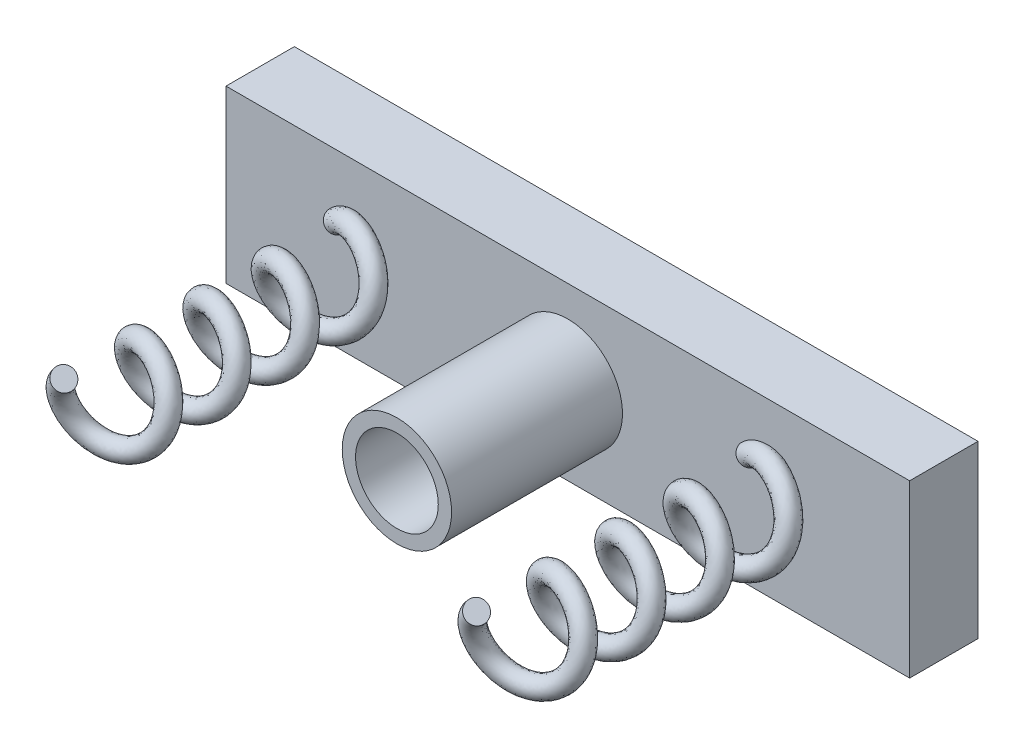
SolidWorks part; units mm, degrees
ref_plane "Front" through (0, 0, 0) normal (0, 0, 1) x (1, 0, 0)
ref_plane "Top" through (0, 0, 0) normal (0, 1, 0) x (1, 0, 0)
ref_plane "Right" through (0, 0, 0) normal (1, 0, 0) x (0, 0, -1)
sketch "草图1" plane through (0, 0, 0) normal (0, 0, 1) x (1, 0, 0)
  line L1 (-50, -12.5) -> (50, -12.5)
  line L2 (-50, -12.5) -> (-50, 12.5)
  line L3 (-50, 12.5) -> (50, 12.5)
  line L4 (50, -12.5) -> (50, 12.5)
  line L5 (-50, -12.5) -> (50, 12.5) construction
  line L6 (-50, 12.5) -> (50, -12.5) construction
  point P0 (0, 0)
extrude "凸台-拉伸1" add sketch "草图1" along normal blind 10
sketch "草图2" plane through (0, 0, 10) normal (0, 0, 1) x (1, 0, 0)
  circle A1 centre (-30, 0) radius 5
curve "螺旋线/涡状线1" pitch 10 height 40 turns 4
ref_plane "基准面1" through (-33.5355, 3.5355, 50) normal (0.6738, 0.6738, 0.3033) x (0.2145, 0.2145, -0.9529)
sketch "草图17" plane through (-33.5355, 3.5355, 50) normal (0.6738, 0.6738, 0.3033) x (0.2145, 0.2145, -0.9529)
  circle A0 centre (-0.0668, 0.1438) radius 1.5
sweep "扫描2" add profiles "草图17" path "螺旋线/涡状线1"
sketch "草图18" plane through (0, 0, 10) normal (0, 0, 1) x (1, 0, 0)
  circle A1 centre (30, 0) radius 5
curve "螺旋线/涡状线2" pitch 10 height 40 turns 4
ref_plane "基准面2" through (26.4645, 3.5355, 50) normal (0.6738, 0.6738, 0.3033) x (0.2145, 0.2145, -0.9529)
sketch "草图20" plane through (26.4645, 3.5355, 50) normal (0.6738, 0.6738, 0.3033) x (0.2145, 0.2145, -0.9529)
  circle A0 centre (0.3821, 0.3712) radius 1.5
sweep "扫描3" add profiles "草图20" path "螺旋线/涡状线2"
sketch "草图21" plane through (0, 0, 10) normal (0, 0, 1) x (1, 0, 0)
  circle A0 centre (0, 0) radius 7.9976
extrude "凸台-拉伸2" add sketch "草图21" along normal blind 25
sketch "草图22" plane through (0, 0, 35) normal (0, 0, 1) x (1, 0, 0)
  circle A0 centre (0, 0) radius 6.05
extrude "切除-拉伸1" cut sketch "草图22" against normal blind 40
